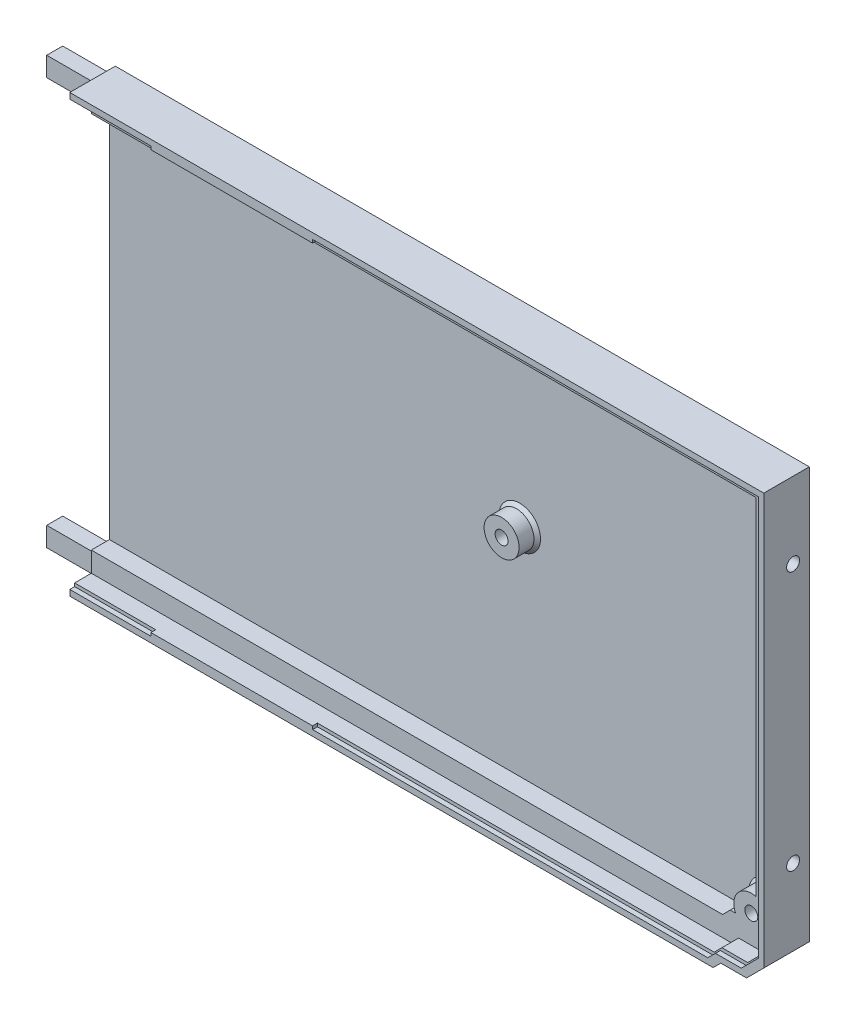
SolidWorks part; units mm, degrees
ref_plane "Přední rovina" through (0, 0, 0) normal (0, 0, 1) x (1, 0, 0)
ref_plane "Horní rovina" through (0, 0, 0) normal (0, 1, 0) x (1, 0, 0)
ref_plane "Pravá rovina" through (0, 0, 0) normal (1, 0, 0) x (0, 0, -1)
sketch "Skica3" plane through (0, 0, 0) normal (0, 0, 1) x (1, 0, 0)
  line L0 (0, 0) -> (415.1053, 0) construction
  line L1 (415.1053, 0) -> (416.6927, -1.5875) construction
  line L2 (416.6927, -1.5875) -> (416.6927, -119.8485) construction
  line L3 (0, 0) -> (-1.5875, -1.5875) construction
  line L4 (-1.5875, -1.5875) -> (-1.5875, -119.8485) construction
  line L5 (-1.5875, -119.8485) -> (0.7934, -122.2292) construction
  line L6 (0.7934, -122.2292) -> (8.7304, -122.2292) construction
  line L7 (8.7304, -122.2292) -> (11.1113, -124.61) construction
  line L8 (11.1113, -124.61) -> (403.9933, -124.61) construction
  line L9 (403.9933, -124.61) -> (406.3744, -122.2294) construction
  line L10 (406.3744, -122.2294) -> (414.3114, -122.2294) construction
  line L11 (416.6927, -119.8485) -> (414.3114, -122.2294) construction
  line L12 (2.4125, -4) -> (412.6927, -4)
  line L13 (412.6927, -4) -> (412.6927, -4)
  line L14 (412.6927, -4) -> (412.6927, -118.1914)
  line L15 (412.6927, -118.1914) -> (412.6547, -118.2294)
  line L16 (404.7177, -118.2294) -> (412.6547, -118.2294)
  line L17 (402.3367, -120.61) -> (404.7177, -118.2294)
  line L18 (12.7681, -120.61) -> (402.3367, -120.61)
  line L19 (10.3872, -118.2292) -> (12.7681, -120.61)
  line L20 (2.4502, -118.2292) -> (10.3872, -118.2292)
  line L21 (2.4125, -118.1915) -> (2.4502, -118.2292)
  line L22 (2.4125, -4) -> (2.4125, -118.1915)
  line L23 (2.4125, -4) -> (2.4125, -4)
  line L24 (-1.5875, -119.8485) -> (415.1053, 0) construction
  line L26 (0, 0) -> (416.6927, -119.8485) construction
  dimension "D1" = 135
  dimension "D2" = 135
  dimension "D3" = 4
  dimension "D4" = 2.245
  dimension "D5" = 2.245
  dimension "D6" = 118.261
  dimension "D7" = 118.261
  dimension "D8" = 3.367
  dimension "D9" = 7.937
  dimension "D10" = 3.367
  dimension "D11" = 392.882
  dimension "D12" = 3.367
  dimension "D13" = 7.937
  dimension "D14" = 3.3674
extrude "Přidat vysunutím1" add sketch "Skica3" along normal blind 5.6
shell "Skořepina1" thickness 1.8 removed face at (207.5525, -95.852, 5.6) outward yes
sketch "Skica7" plane through (0, 0, 5.6) normal (0, 0, 1) x (1, 0, 0)
  line L20 (-6.5875, 5) -> (-6.5875, -121.9196)
  line L21 (-6.5875, -121.9196) -> (-1.2775, -127.2292)
  line L22 (-1.2775, -127.2292) -> (6.6595, -127.2292)
  line L23 (6.6595, -127.2292) -> (9.0403, -129.61)
  line L24 (9.0403, -129.61) -> (406.0641, -129.61)
  line L25 (406.0641, -129.61) -> (408.4452, -127.2294)
  line L26 (408.4452, -127.2294) -> (416.3822, -127.2294)
  line L27 (416.3822, -127.2294) -> (421.6927, -121.9198)
  line L28 (421.6927, -121.9198) -> (421.6927, 5)
  line L29 (421.6927, 5) -> (-6.5875, 5)
  line L30 (-6.5875, 5) -> (-6.5875, -121.9196)
  line L31 (-6.5875, -121.9196) -> (-1.2775, -127.2292)
  line L32 (-1.2775, -127.2292) -> (6.6595, -127.2292)
  line L33 (6.6595, -127.2292) -> (9.0403, -129.61)
  line L34 (9.0403, -129.61) -> (406.0641, -129.61)
  line L35 (406.0641, -129.61) -> (408.4452, -127.2294)
  line L36 (408.4452, -127.2294) -> (416.3822, -127.2294)
  line L37 (416.3822, -127.2294) -> (421.6927, -121.9198)
  line L38 (421.6927, -121.9198) -> (421.6927, 5)
  line L39 (421.6927, 5) -> (-6.5875, 5)
  line L40 (-3.7875, 2.2) -> (-3.7875, -120.7598)
  line L41 (-3.7875, -120.7598) -> (-0.1178, -124.4292)
  line L42 (-0.1178, -124.4292) -> (7.8192, -124.4292)
  line L43 (7.8192, -124.4292) -> (10.2001, -126.81)
  line L44 (10.2001, -126.81) -> (404.9045, -126.81)
  line L45 (404.9045, -126.81) -> (407.2855, -124.4294)
  line L46 (407.2855, -124.4294) -> (415.2225, -124.4294)
  line L47 (415.2225, -124.4294) -> (418.8927, -120.7598)
  line L48 (418.8927, -120.7598) -> (418.8927, 2.2)
  line L49 (418.8927, 2.2) -> (-3.7875, 2.2)
  line L50 (-3.7875, 2.2) -> (-3.7875, -120.7598)
  line L51 (-3.7875, -120.7598) -> (-0.1178, -124.4292)
  line L52 (-0.1178, -124.4292) -> (7.8192, -124.4292)
  line L53 (7.8192, -124.4292) -> (10.2001, -126.81)
  line L54 (10.2001, -126.81) -> (404.9045, -126.81)
  line L55 (404.9045, -126.81) -> (407.2855, -124.4294)
  line L56 (407.2855, -124.4294) -> (415.2225, -124.4294)
  line L57 (415.2225, -124.4294) -> (418.8927, -120.7598)
  line L58 (418.8927, -120.7598) -> (418.8927, 2.2)
  line L59 (418.8927, 2.2) -> (-3.7875, 2.2)
  dimension "D2" = 4.4
  dimension "D1" = 7.2
extrude "Přidat vysunutím3" add sketch "Skica7" along normal blind 5.15 separate body
sketch "Skica8" plane through (0, 0, 5.6) normal (0, 0, -1) x (-1, 0, 0)
  line L0 (-421.6927, 5) -> (6.5875, 5)
  line L1 (6.5875, 5) -> (6.5875, -121.9196)
  line L2 (6.5875, 5) -> (6.5875, -121.9196) construction
  line L3 (6.5875, -121.9196) -> (1.2775, -127.2292)
  line L4 (1.2775, -127.2292) -> (-6.6595, -127.2292)
  line L5 (-6.6595, -127.2292) -> (-9.0403, -129.61)
  line L6 (-9.0403, -129.61) -> (-406.0641, -129.61)
  line L7 (-406.0641, -129.61) -> (-408.4452, -127.2294)
  line L8 (-408.4452, -127.2294) -> (-416.3822, -127.2294)
  line L9 (-416.3822, -127.2294) -> (-421.6927, -121.9198)
  line L10 (-421.6927, -121.9198) -> (-421.6927, 5)
  line L11 (-0.6125, -2.2) -> (-0.6125, -118.9371)
  line L12 (-414.4927, -2.2) -> (-0.6125, -2.2) construction
  line L13 (-0.6125, -2.2) -> (-0.6125, -118.9371) construction
  line L14 (-0.6125, -118.9371) -> (-1.7047, -120.0292)
  line L15 (-1.7047, -120.0292) -> (-9.6417, -120.0292)
  line L16 (-9.6417, -120.0292) -> (-12.0226, -122.41)
  line L17 (-12.0226, -122.41) -> (-403.0822, -122.41)
  line L18 (-403.0822, -122.41) -> (-405.4632, -120.0294)
  line L19 (-405.4632, -120.0294) -> (-413.4002, -120.0294) construction
  line L20 (-405.4632, -120.0294) -> (-413.4002, -120.0294)
  line L21 (-413.4002, -120.0294) -> (-414.4927, -118.9371) construction
  line L22 (-413.4002, -120.0294) -> (-414.4927, -118.9371)
  line L23 (-414.4927, -118.9371) -> (-414.4927, -2.2)
  line L24 (-414.4927, -2.2) -> (-0.6125, -2.2)
extrude "Přidat vysunutím4" add sketch "Skica8" along normal up to surface (7.4 mm away) up to face at (207.5525, -96.7211, -1.8)
sketch "Skica11" plane through (0, 0, 10.75) normal (0, 0, 1) x (1, 0, 0)
  line L0 (207.5526, 3.195) -> (207.5526, 5) construction
  line L1 (421.6927, 5) -> (-6.5875, 5) construction
  line L2 (207.5522, -127.805) -> (207.5522, -129.61) construction
  line L3 (9.0403, -129.61) -> (406.0641, -129.61) construction
  line L4 (-4.9474, -58.4598) -> (-6.5875, -58.4598) construction
  line L5 (-6.5875, 5) -> (-6.5875, -121.9196) construction
  line L6 (420.0526, -58.4599) -> (421.6927, -58.4599) construction
  line L7 (421.6927, -121.9198) -> (421.6927, 5) construction
  line L8 (404.9045, -126.81) -> (407.2855, -124.4294) construction
  line L9 (415.2225, -124.4294) -> (418.8927, -120.7598) construction
  line L10 (7.8192, -124.4292) -> (10.2001, -126.81) construction
  line L11 (-3.7875, -120.7598) -> (-0.1178, -124.4292) construction
  line L13 (407.2855, -124.4294) -> (415.2225, -124.4294) construction
  line L14 (-0.1178, -124.4292) -> (7.8192, -124.4292) construction
  line L30 (420.0526, 3.195) -> (-4.9474, 3.195)
  line L31 (-4.9474, 3.195) -> (-4.9474, -120.1146)
  line L32 (-4.9474, -120.1146) -> (-0.24, -124.8217)
  line L33 (-0.24, -124.8217) -> (7.697, -124.8217)
  line L34 (7.697, -124.8217) -> (10.6804, -127.805)
  line L35 (10.6804, -127.805) -> (404.4241, -127.805)
  line L36 (404.4241, -127.805) -> (406.8051, -125.4244)
  line L37 (406.8051, -125.4244) -> (414.7421, -125.4244)
  line L38 (414.7421, -125.4244) -> (420.0526, -120.1148)
  line L39 (420.0526, -120.1148) -> (420.0526, 3.195)
  line L45 (421.6927, 5) -> (-6.5875, 5)
  line L46 (-6.5875, 5) -> (-6.5875, -121.9196)
  line L47 (-6.5875, -121.9196) -> (-1.2775, -127.2292)
  line L48 (-1.2775, -127.2292) -> (6.6595, -127.2292)
  line L49 (6.6595, -127.2292) -> (9.0403, -129.61)
  line L50 (9.0403, -129.61) -> (406.0641, -129.61)
  line L51 (406.0641, -129.61) -> (408.4452, -127.2294)
  line L52 (408.4452, -127.2294) -> (416.3822, -127.2294)
  line L53 (416.3822, -127.2294) -> (421.6927, -121.9198)
  line L54 (421.6927, -121.9198) -> (421.6927, 5)
  line L55 (421.6927, 5) -> (-6.5875, 5)
  line L56 (-6.5875, 5) -> (-6.5875, -121.9196)
  line L57 (-6.5875, -121.9196) -> (-1.2775, -127.2292)
  line L58 (-1.2775, -127.2292) -> (6.6595, -127.2292)
  line L59 (6.6595, -127.2292) -> (9.0403, -129.61)
  line L60 (9.0403, -129.61) -> (406.0641, -129.61)
  line L61 (406.0641, -129.61) -> (408.4452, -127.2294)
  line L62 (408.4452, -127.2294) -> (416.3822, -127.2294)
  line L63 (416.3822, -127.2294) -> (421.6927, -121.9198)
  line L64 (421.6927, -121.9198) -> (421.6927, 5)
  point P0 (207.5523, -63.11)
  point P2 (207.5523, -63.11)
  dimension "D1" = 131
  dimension "D2" = 425
  dimension "D3" = 0
extrude "Přidat vysunutím5" add sketch "Skica11" along normal blind 1.5
sketch "Skica14" plane through (0, 0, 10.75) normal (0, 0, 1) x (1, 0, 0)
  line L0 (418.8927, 2.2) -> (-3.7875, 2.2) construction
  line L1 (182.5326, 2.2) -> (132.6326, 2.2)
  line L2 (182.5326, 2.2) -> (182.5326, 3.195)
  line L3 (182.5326, 3.195) -> (132.6326, 3.195)
  line L4 (132.6326, 2.2) -> (132.6326, 3.195)
  line L5 (420.0526, 3.195) -> (-4.9474, 3.195) construction
  line L6 (418.8927, 2.2) -> (-3.7875, 2.2) construction
  line L7 (232.5726, 2.2) -> (282.4726, 2.2)
  line L8 (232.5726, 2.2) -> (232.5726, 3.195)
  line L9 (232.5726, 3.195) -> (282.4726, 3.195)
  line L10 (282.4726, 2.2) -> (282.4726, 3.195)
  line L11 (207.5526, 3.195) -> (207.5522, -127.805) construction
  line L12 (10.6804, -127.805) -> (404.4241, -127.805) construction
  line L13 (10.2001, -126.81) -> (404.9045, -126.81) construction
  line L14 (232.5722, -126.81) -> (282.4722, -126.81)
  line L15 (232.5722, -126.81) -> (232.5722, -127.805)
  line L16 (232.5722, -127.805) -> (282.4722, -127.805)
  line L17 (282.4722, -126.81) -> (282.4722, -127.805)
  line L18 (10.6804, -127.805) -> (404.4241, -127.805) construction
  line L20 (182.5322, -126.81) -> (132.6322, -126.81)
  line L21 (182.5322, -126.81) -> (182.5322, -127.805)
  line L22 (182.5322, -127.805) -> (132.6322, -127.805)
  line L23 (132.6322, -126.81) -> (132.6322, -127.805)
  dimension "D1" = 49.9
  dimension "D2" = 49.9
  dimension "D3" = 25.02
  dimension "D4" = 25.02
  dimension "D5" = 49.9
  dimension "D6" = 49.9
  dimension "D7" = 25.02
  dimension "D8" = 25.02
extrude "Přidat vysunutím6" add sketch "Skica14" along normal up to surface (1.5 mm away) up to face at (207.5524, -100.1977, 12.25)
sketch "Skica15" plane through (0, 0, 0) normal (0, 0, 1) x (1, 0, 0)
  line L1 (34.9015, 4.5) -> (37.9015, 4.5)
  line L2 (34.9015, 4.5) -> (34.9015, -4.5)
  line L3 (34.9015, -4.5) -> (37.9015, -4.5)
  line L4 (37.9015, 4.5) -> (37.9015, -4.5)
  line L5 (34.9015, 4.5) -> (37.9015, -4.5) construction
  line L6 (34.9015, -4.5) -> (37.9015, 4.5) construction
  line L20 (-1.5875, 0) -> (-1.5875, -119.8485)
  line L21 (-1.5875, -119.8485) -> (0.7934, -122.2292)
  line L22 (0.7934, -122.2292) -> (8.7304, -122.2292)
  line L23 (8.7304, -122.2292) -> (11.1113, -124.61)
  line L24 (11.1113, -124.61) -> (403.9933, -124.61)
  line L25 (403.9933, -124.61) -> (406.3744, -122.2294)
  line L26 (406.3744, -122.2294) -> (414.3114, -122.2294)
  line L27 (414.3114, -122.2294) -> (416.6927, -119.8485)
  line L28 (416.6927, -119.8485) -> (416.6927, 0)
  line L29 (416.6927, 0) -> (-1.5875, 0)
  line L30 (-1.5875, 0) -> (-1.5875, -119.8485) construction
  line L31 (-1.5875, -119.8485) -> (0.7934, -122.2292) construction
  line L32 (0.7934, -122.2292) -> (8.7304, -122.2292) construction
  line L33 (8.7304, -122.2292) -> (11.1113, -124.61) construction
  line L34 (11.1113, -124.61) -> (403.9933, -124.61) construction
  line L35 (403.9933, -124.61) -> (406.3744, -122.2294) construction
  line L36 (406.3744, -122.2294) -> (414.3114, -122.2294) construction
  line L37 (414.3114, -122.2294) -> (416.6927, -119.8485) construction
  line L38 (416.6927, -119.8485) -> (416.6927, 0) construction
  line L39 (416.6927, 0) -> (-1.5875, 0) construction
  circle A0 centre (3.9685, -115.9542) radius 5.4
  circle A1 centre (33.4915, -69.051) radius 5.4
  circle A2 centre (411.1977, -115.8794) radius 5.4
  circle A3 centre (334.1477, -53.972) radius 5.4
  point P2 (-1.4315, -115.9542)
  point P3 (3.9685, -121.3542)
  point P4 (28.0915, -69.051)
  point P8 (33.4915, -74.451)
  point P12 (411.1977, -121.2794)
  point P13 (416.5977, -115.8794)
  point P17 (334.1477, -48.572)
  point P19 (339.5477, -53.972)
  point P21 (36.4015, 0)
  point P23 (36.4015, 0)
  dimension "D2" = 0.156
  dimension "D4" = 10.8
  dimension "D7" = 10.8
  dimension "D10" = 10.8
  dimension "D13" = 10.8
  dimension "D3" = 0.875
  dimension "D5" = 29.679
  dimension "D6" = 50.159
  dimension "D8" = 0.095
  dimension "D9" = 0.95
  dimension "D11" = 77.145
  dimension "D12" = 48.572
  dimension "D14" = 37.989
  dimension "D15" = 9
  dimension "D16" = 3
  dimension "D1" = 4
extrude "Přidat vysunutím7" add sketch "Skica15" along normal blind 5.6
sketch "Skica16" plane through (0, 0, 5.6) normal (0, 0, 1) x (1, 0, 0)
  circle A0 centre (3.9685, -115.9542) radius 2
  circle A1 centre (33.4915, -69.051) radius 2
  circle A2 centre (334.1477, -53.972) radius 2
  circle A3 centre (411.1977, -115.8794) radius 2
  dimension "D1" = 4
  dimension "D2" = 4
  dimension "D3" = 4
  dimension "D4" = 4
extrude "Odebrat vysunutím1" cut sketch "Skica16" against normal blind 5.75
chamfer "Zkosení1" distance 1 angle 45 4 edges at (407.0694, -112.3984, 0) (8.0492, -112.4175, 0) (38.8915, -69.051, 0) (339.5477, -53.972, 0)
sketch "Skica17" plane through (0, 0, 5.6) normal (0, 0, 1) x (1, 0, 0)
  line L0 (34.9015, -4.5) -> (37.9015, -4.5) construction
  line L1 (24.4015, -11.2) -> (48.4015, -11.2)
  line L2 (24.4015, -11.2) -> (24.4015, 2.2)
  line L3 (24.4015, 2.2) -> (48.4015, 2.2)
  line L4 (48.4015, -11.2) -> (48.4015, 2.2)
  line L5 (24.4015, -11.2) -> (48.4015, 2.2) construction
  line L6 (24.4015, 2.2) -> (48.4015, -11.2) construction
  line L7 (418.8927, 2.2) -> (-3.7875, 2.2) construction
  point P0 (36.4015, -4.5)
  dimension "D1" = 24
extrude "Odebrat vysunutím2" cut sketch "Skica17" against normal blind 1.6
sketch "Skica18" plane through (0, -4.5, 0) normal (0, -1, 0) x (1, 0, 0)
  line L0 (33.6515, 4) -> (39.1515, 4) construction
  line L1 (37.9015, 4) -> (34.9015, 4) construction
  line L2 (37.9015, 4) -> (48.4015, 4) construction
  line L3 (33.6515, 7.5) -> (39.1515, 7.5)
  line L4 (33.6515, 0.5) -> (39.1515, 0.5)
  arc A0 (33.6515, 7.5) -> (33.6515, 0.5) centre (33.6515, 4) ccw
  arc A1 (39.1515, 0.5) -> (39.1515, 7.5) centre (39.1515, 4) ccw
  point P6 (36.4015, 4)
  point P11 (30.1515, 4)
  point P12 (42.6515, 4)
  dimension "D1" = 12.5
  dimension "D2" = 7
extrude "Odebrat vysunutím3" cut sketch "Skica18" against normal up to surface (9.5 mm away) up to face at (207.5526, 5, 5.225)
sketch "Skica23" plane through (-6.5875, 0, 0) normal (-1, 0, 0) x (0, 0, 1)
  line L2 (-1.8, 5) -> (-1.8, -121.9196) construction
  line L4 (-1.8, -58.4598) -> (12.25, -58.4598) construction
  line L5 (12.25, 5) -> (12.25, -121.9196) construction
  circle A0 centre (3.2, -18.4598) radius 2
  circle A1 centre (3.2, -98.4598) radius 2
  point P8 (-1.8, -58.4598)
  dimension "D2" = 4
  dimension "D3" = 4
  dimension "D1" = 40
  dimension "D4" = 5
extrude "Odebrat vysunutím4" cut sketch "Skica23" against normal blind 5.7
sketch "Skica24" plane through (421.6927, 0, 0) normal (1, 0, 0) x (0, 0, -1)
  line L0 (1.8, -58.4599) -> (-12.25, -58.4599) construction
  line L1 (1.8, -121.9198) -> (1.8, 5) construction
  line L2 (-12.25, -121.9198) -> (-12.25, 5) construction
  circle A0 centre (-3.2, -18.4599) radius 2
  circle A1 centre (-3.2, -98.4599) radius 2
  dimension "D1" = 4
  dimension "D2" = 4
  dimension "D3" = 40
  dimension "D4" = 5
extrude "Odebrat vysunutím5" cut sketch "Skica24" against normal blind 5.7
sketch "Skica25" plane through (0, 0, -1.8) normal (0, 0, -1) x (-1, 0, 0)
  line L0 (-421.6927, -121.9198) -> (-421.6927, 5) construction
  line L1 (-421.6927, 5) -> (6.5875, 5) construction
  line L2 (6.5875, 5) -> (6.5875, -121.9196) construction
  line L3 (-9.0403, -129.61) -> (-406.0641, -129.61) construction
  circle A0 centre (-401.6927, -15) radius 6.25
  circle A1 centre (-13.4125, -15) radius 6.25
  circle A2 centre (-388.4452, -109.61) radius 6.25
  circle A3 centre (-26.6595, -109.61) radius 6.25
  dimension "D1" = 12.5
  dimension "D2" = 12.5
  dimension "D3" = 12.5
  dimension "D4" = 12.5
  dimension "D5" = 20
  dimension "D6" = 20
  dimension "D7" = 20
  dimension "D8" = 20
  dimension "D9" = 20
  dimension "D10" = 20
  dimension "D11" = 20
  dimension "D12" = 20
extrude "Odebrat vysunutím6" cut sketch "Skica25" against normal blind 1.2
sketch "Skica26" plane through (0, 5, 0) normal (0, 1, 0) x (1, 0, 0)
  line L0 (421.6927, -12.25) -> (-6.5875, -12.25) construction
  line L1 (207.5526, -12.25) -> (-6.5875, -12.25)
  line L2 (207.5526, -12.25) -> (207.5526, 1.8)
  line L3 (207.5526, 1.8) -> (-6.5875, 1.8)
  line L4 (-6.5875, -12.25) -> (-6.5875, 1.8)
extrude "Odebrat vysunutím7" cut sketch "Skica26" against normal through all
sketch "Skica27" plane through (207.5526, 0, 0) normal (-1, 0, 0) x (0, 0, 1)
  line L0 (0, -4) -> (-1.8, -4) construction
  line L1 (-1.8, -129.61) -> (-1.8, 5) construction
  line L2 (-1.8, -4) -> (5.6, 5) construction
  line L3 (12.25, 5) -> (-1.8, 5) construction
  line L4 (5.6, 5) -> (5.6, 2.2) construction
  line L5 (-1.8, 5) -> (5.6, -4) construction
  line L6 (0, -120.61) -> (-1.8, -120.61) construction
  line L7 (-0.5667, -2.5) -> (4.3667, -2.5)
  line L8 (-0.5667, -2.5) -> (-0.5667, 3.5)
  line L9 (-0.5667, 3.5) -> (4.3667, 3.5)
  line L10 (4.3667, -2.5) -> (4.3667, 3.5)
  line L11 (-0.5667, -2.5) -> (4.3667, 3.5) construction
  line L12 (-0.5667, 3.5) -> (4.3667, -2.5) construction
  line L13 (5.6, -126.81) -> (5.6, -129.61) construction
  line L14 (12.25, -129.61) -> (-1.8, -129.61) construction
  line L15 (-1.8, -120.61) -> (5.6, -129.61) construction
  line L16 (-1.8, -129.61) -> (5.6, -120.61) construction
  line L17 (5.6, -120.61) -> (0, -120.61) construction
  line L18 (-0.5667, -128.11) -> (4.3667, -128.11)
  line L19 (-0.5667, -128.11) -> (-0.5667, -122.11)
  line L20 (-0.5667, -122.11) -> (4.3667, -122.11)
  line L21 (4.3667, -128.11) -> (4.3667, -122.11)
  line L22 (-0.5667, -128.11) -> (4.3667, -122.11) construction
  line L23 (-0.5667, -122.11) -> (4.3667, -128.11) construction
  point P14 (1.9, 0.5)
  point P31 (1.9, -125.11)
  dimension "D1" = 1.5
  dimension "D2" = 1.5
extrude "Přidat vysunutím8" add sketch "Skica27" along normal blind 15
